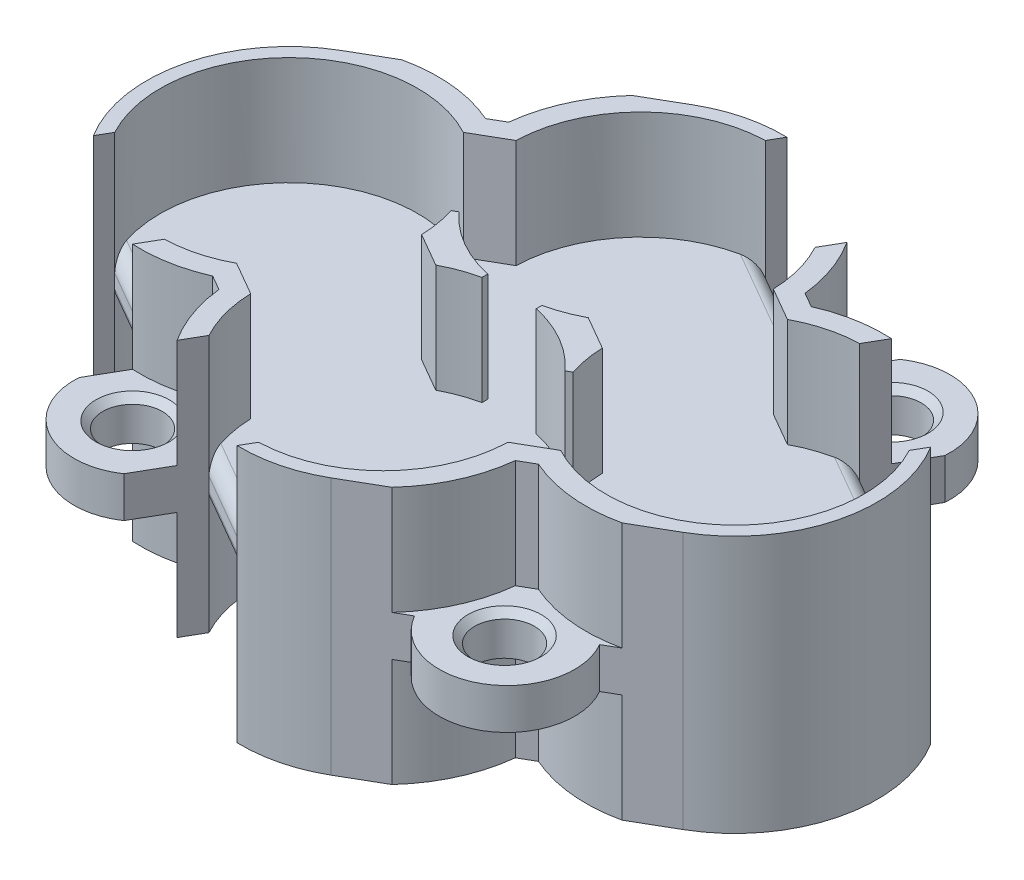
SolidWorks part; units mm, degrees
note: The reader was unsure of these and kept them because the rebuilt part matched: shared geometry of "Sketch1<4>", "Sketch1<6>".
ref_plane "Front Plane" through (0, 0, 0) normal (0, 0, 1) x (1, 0, 0)
ref_plane "Top Plane" through (0, 0, 0) normal (0, 1, 0) x (1, 0, 0)
ref_plane "Right Plane" through (0, 0, 0) normal (1, 0, 0) x (0, 0, -1)
sketch "Sketch1" plane through (0, 0, 0) normal (0, 1, 0) x (1, 0, 0)
  line L0 (-11.9589, 8.369) -> (-9.4955, 9.7913)
  line L1 (-6.9589, -0.2913) -> (-4.4955, 1.131)
  line L2 (-16.4545, 0) -> (0, 9.5) construction
  line L3 (-12.0193, 10.0662) -> (-10.9352, 10.6921)
  line L4 (0, 9.0625) -> (0, -9.0625) construction
  line L5 (-16.4545, 0) -> (16.4545, 0) construction
  line L6 (-5.25, 18.5933) -> (-21.7045, 9.0933)
  line L7 (5.25, -18.5933) -> (21.7045, -9.0933)
  line L8 (-21.7045, -9.0933) -> (-5.25, -18.5933)
  line L9 (5.25, 18.5933) -> (21.7045, 9.0933)
  line L10 (-12.0193, -10.0662) -> (-10.9352, -10.6921)
  line L11 (-16.4545, 0) -> (0, -9.5) construction
  line L12 (0, -19) -> (0, -20)
  line L13 (0, 20) -> (0, 19)
  line L14 (-11.9589, -8.369) -> (-9.4955, -9.7913)
  line L15 (0, 0) -> (-27.9836, 16.1563) construction
  circle A0 centre (-16.4545, 0) radius 9.5
  circle A1 centre (0, 9.5) radius 9.5
  circle A2 centre (16.4545, 0) radius 9.5
  circle A3 centre (0, -9.5) radius 9.5
  arc A4 (-21.7045, 9.0933) -> (-21.7045, -9.0933) centre (-16.4545, 0) ccw
  arc A5 (-5.25, -18.5933) -> (5.25, -18.5933) centre (0, -9.5) ccw
  arc A6 (21.7045, 9.0933) -> (21.7045, -9.0933) centre (16.4545, 0) cw
  arc A7 (-5.25, 18.5933) -> (5.25, 18.5933) centre (0, 9.5) cw
  arc A8 (-18.865, -10.7326) -> (-10.9999, -9.5523) centre (-16.4545, 0) ccw
  arc A9 (-8.0895, 16.9539) -> (-10.9999, 9.5523) centre (0, 9.5) ccw
  circle A12 centre (0, 9.5) radius 11 construction
  circle A13 centre (-16.4545, 0) radius 11 construction
  arc A15 (-10.9999, -9.5523) -> (-8.0895, -16.9539) centre (0, -9.5) ccw
  arc A19 (-10.9999, 9.5523) -> (-18.865, 10.7326) centre (-16.4545, 0) ccw
  dimension "D1" = 19
  dimension "D2" = 19
  dimension "D3" = 19
  dimension "D4" = 19
  dimension "D5" = 10.5
  dimension "D6" = 10.5
  dimension "D7" = 10.5
  dimension "D8" = 10.5
  dimension "D9" = 11
  dimension "D11" = 11
  dimension "D13" = 5
  dimension "D14" = 5
  dimension "D15" = 1.5
  dimension "D16" = 6.5
  dimension "D17" = 5
  dimension "D10" = 1.5
extrude "Boss-Extrude1" add sketch "Sketch1" against normal blind 3
extrude "Boss-Extrude2" add sketch "Sketch1<4>" against normal blind 3 contours A1 | A3
sketch "Sketch1<4>" plane through (0, 0, 0) normal (0, 1, 0) x (1, 0, 0) same geometry as "Sketch1"
extrude "Boss-Extrude3" add sketch "Sketch1<6>" along normal blind 8 and the other way offset from surface (11 mm away) 8
sketch "Sketch1<6>" plane through (0, 0, 0) normal (0, 1, 0) x (1, 0, 0) same geometry as "Sketch1"
sketch "Sketch3" plane through (0, 0, 0) normal (0, 1, 0) x (1, 0, 0)
  line L2 (-18.865, -10.7326) -> (-8.0895, -16.9539) construction
  line L3 (-8.0895, 16.9539) -> (-18.865, 10.7326) construction
  line L5 (-17.8074, -11.3433) -> (-9.1471, -16.3433)
  line L6 (-17.8074, 11.3433) -> (-9.1471, 16.3433)
  line L7 (-10.9999, -9.5523) -> (-12.1217, -11.4953) construction
  line L8 (-16.4545, 0) -> (0, -9.5) construction
  line L9 (-12.0193, -10.0662) -> (-10.9352, -10.6921) construction
  line L10 (-10.9999, 9.5523) -> (-11.9287, 11.1612) construction
  line L11 (-16.4545, 0) -> (0, 9.5) construction
  line L12 (-12.0193, 10.0662) -> (-10.9352, 10.6921) construction
  arc A0 (-17.8074, -11.3433) -> (-9.1471, -16.3433) centre (-13.4772, -13.8433) ccw
  arc A1 (-17.8074, 11.3433) -> (-9.1471, 16.3433) centre (-13.4772, 13.8433) cw
  dimension "D1" = 4
  dimension "D2" = 5
  dimension "D4" = 5
  dimension "D3" = 4
extrude "Boss-Extrude4" add sketch "Sketch3" against normal blind 3
sketch "Sketch4" plane through (0, 0, 0) normal (0, 1, 0) x (1, 0, 0)
  line L0 (-11.4772, -10.3792) -> (-13.7272, -14.2763)
  line L1 (-12.0193, -10.0662) -> (-10.9352, -10.6921) construction
  line L2 (-12.0193, -10.0662) -> (-10.9352, -10.6921) construction
  line L3 (-13.7272, 14.2763) -> (-11.4772, 10.3792)
  line L4 (-12.0193, 10.0662) -> (-10.9352, 10.6921) construction
  circle A0 centre (-13.7272, -14.2763) radius 2.2
  circle A1 centre (-13.7272, 14.2763) radius 2.2
  dimension "D1" = 4.4
  dimension "D3" = 4.4
  dimension "D2" = 4.5
  dimension "D4" = 4.5
extrude "Cut-Extrude1" cut sketch "Sketch4" against normal up to next
chamfer "Chamfer1" distance 0.5 angle 45 2 edges at (-13.7272, 0, -12.0763) (-13.7272, 0, 16.4763)
mirror "Mirror1" about plane through (0, 0, 0) normal (1, 0, 0) of "Chamfer1", "Cut-Extrude1", "Boss-Extrude3", "Boss-Extrude4"
sketch "Sketch5" plane through (0, 8, 0) normal (0, 1, 0) x (1, 0, 0)
  line L0 (-17.6743, 0) -> (16.6223, 0) construction
  line L1 (0, 0) -> (0, -9.5473) construction
  line L2 (-16.4545, 0) -> (0, -9.5) construction
  line L3 (-16.4545, 0) -> (-23.6771, -12.5099) construction
  line L4 (0, -9.5) -> (-7.4901, -22.4732) construction
  line L5 (-24.8235, -4.4955) -> (-16.1632, -9.4955)
  line L6 (-24.8235, -4.4955) -> (-27.1243, -8.4807)
  line L7 (-16.1632, -9.4955) -> (-18.4641, -13.4807)
  line L8 (-27.1243, -8.4807) -> (-18.4641, -13.4807)
  line L9 (-8.369, -13.9955) -> (0.2913, -18.9955)
  line L10 (-8.369, -13.9955) -> (-10.6699, -17.9807)
  line L11 (0.2913, -18.9955) -> (-2.0096, -22.9807)
  line L12 (-10.6699, -17.9807) -> (-2.0096, -22.9807)
  line L15 (16.4545, 0) -> (21.7045, 9.0933) construction
  line L16 (0, 9.5) -> (5.25, 18.5933) construction
  line L17 (-0.2913, 18.9955) -> (8.369, 13.9955)
  line L18 (-0.2913, 18.9955) -> (2.0096, 22.9807)
  line L19 (8.369, 13.9955) -> (10.6699, 17.9807)
  line L20 (2.0096, 22.9807) -> (10.6699, 17.9807)
  line L21 (16.1632, 9.4955) -> (24.8235, 4.4955)
  line L22 (16.1632, 9.4955) -> (18.4641, 13.4807)
  line L23 (24.8235, 4.4955) -> (27.1243, 8.4807)
  line L24 (18.4641, 13.4807) -> (27.1243, 8.4807)
  arc A0 (-11.9589, 8.369) -> (-11.9589, -8.369) centre (-16.4545, 0) ccw construction
  arc A1 (-9.4955, -9.7913) -> (9.4955, -9.7913) centre (0, -9.5) ccw construction
  arc A2 (11.9589, -8.369) -> (11.9589, 8.369) centre (16.4545, 0) ccw construction
  arc A3 (-17.8074, -11.3433) -> (-9.1471, -16.3433) centre (-13.4772, -13.8433) ccw construction
  arc A4 (-9.4955, -9.7913) -> (9.4955, -9.7913) centre (0, -9.5) ccw construction
  arc A5 (17.8074, 11.3433) -> (9.1471, 16.3433) centre (13.4772, 13.8433) ccw construction
  circle A7 centre (0, 9.5) radius 9.5 construction
  point P1 (-16.4545, 0)
  point P9 (0, -9.5)
  dimension "D1" = 10
  dimension "D3" = 5
  dimension "D4" = 5
  dimension "D5" = 10
  dimension "D8" = 10
  dimension "D9" = 5
  dimension "D11" = 10
  dimension "D12" = 5
extrude "Cut-Extrude2" cut sketch "Sketch5" against normal up to next
fillet "Fillet1" radius 1 8 edges at (-20.4934, 0, 6.9955) (-20.4934, -3, 6.9955) (-4.0389, 0, 16.4955) (-4.0389, -3, 16.4955) (4.0389, 0, -16.4955) (4.0389, -3, -16.4955) (20.4934, 0, -6.9955) (20.4934, -3, -6.9955)
sketch "Sketch6" plane through (0, 0, 0) normal (0, 1, 0) x (1, 0, 0)
  line L8 (-16.4545, 0) -> (0, 9.5) construction
  line L11 (-6.9589, 0.2913) -> (-4.4955, -1.131)
  line L12 (-16.4545, 0) -> (0, -9.5) construction
  line L13 (-7.0429, 3.1244) -> (-7.4116, 2.9115)
  line L14 (-2, 0.2129) -> (-2, -0.2129)
  line L15 (-16.4545, 0) -> (16.4545, 0) construction
  line L16 (4.4955, 1.131) -> (6.9589, -0.2913)
  line L17 (0, 9.5) -> (16.4545, 0) construction
  line L18 (173205.0808, -100000) -> (-173233.0643, 100016.1563) construction
  line L19 (2, 0.2129) -> (2, -0.2129)
  line L20 (7.4116, -2.9115) -> (7.0429, -3.1244)
  arc A2 (-8.2272, 4.75) -> (0, 0) centre (0, 9.5) ccw
  circle A16 centre (0, 9.5) radius 9.5 construction
  circle A24 centre (-16.4545, 0) radius 9.5 construction
  circle A25 centre (0, -9.5) radius 9.5 construction
  arc A26 (-6.9589, 0.2913) -> (-8.2272, 4.75) centre (-16.4545, 0) ccw
  arc A27 (0, 0) -> (-4.4955, -1.131) centre (0, -9.5) ccw
  circle A28 centre (16.4545, 0) radius 9.5 construction
  arc A29 (4.4955, 1.131) -> (0, 0) centre (0, 9.5) cw
  arc A30 (8.2272, -4.75) -> (6.9589, -0.2913) centre (16.4545, 0) cw
  arc A31 (8.2272, -4.75) -> (0, 0) centre (0, -9.5) ccw
  dimension "D1" = 5
  dimension "D2" = 2
  dimension "D3" = 2
  dimension "D4" = 10
  dimension "D5" = 2
  dimension "D6" = 2
extrude "Boss-Extrude5" add sketch "Sketch6" along normal blind 8 and the other way offset from surface (11 mm away) 8 contours A27 L14 A2 L13 A26 L11 | A31 L20 A30 L16 A29 L19 other way up to face at (13.7272, -3, 16.4763)
equation "\"D2@Sketch1\"=\"D1@Sketch1\""
equation "\"D3@Sketch1\"=\"D1@Sketch1\""
equation "\"D4@Sketch1\"=\"D1@Sketch1\""
